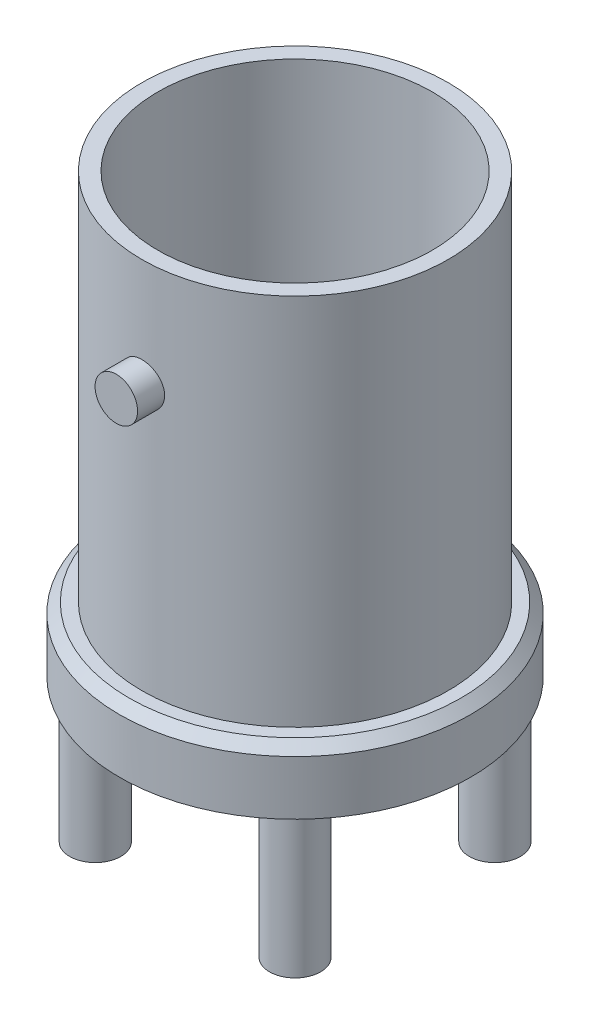
SolidWorks part; units mm, degrees
note: The reader was unsure of these and kept them because the rebuilt part matched: shared geometry of "Sketch5<3>".
ref_plane "Front Plane" through (0, 0, 0) normal (0, 0, 1) x (1, 0, 0)
ref_plane "Top Plane" through (0, 0, 0) normal (0, 1, 0) x (1, 0, 0)
ref_plane "Right Plane" through (0, 0, 0) normal (1, 0, 0) x (0, 0, -1)
sketch "Sketch1" plane through (0, 0, 0) normal (1, 0, 0) x (0, 0, -1)
  line L0 (0, 0) -> (0, 2)
  line L1 (4.3, 13.7) -> (4.8, 13.7)
  line L2 (4.8, 13.7) -> (4.8, 2)
  line L3 (4.8, 2) -> (5.5, 2)
  line L5 (5.5, 2) -> (5.5, 0)
  line L6 (5.5, 0) -> (0, 0)
  line L7 (4.3, 13.7) -> (4.3, 2)
  line L8 (4.3, 2) -> (1.7239, 2)
  line L9 (1.7239, 2) -> (1.7239, 9.3845)
  line L10 (1.7239, 9.3845) -> (0.2863, 9.3845)
  line L11 (0.2863, 9.3845) -> (0.2863, 2)
  line L14 (0.2863, 2) -> (0, 2)
  dimension "D1" = 5.5
  dimension "D2" = 4.8
  dimension "D3" = 2
  dimension "D4" = 13.7
  dimension "D5" = 0.5
revolve "Revolve1" add sketch "Sketch1" angle 360 about L0
ref_plane "Plane1" through (0, 0, 4.8) normal (0, 0, 1) x (1, 0, 0)
sketch "Sketch4" plane through (0, 0, 4.8) normal (0, 0, 1) x (1, 0, 0)
  line L0 (0, 2) -> (0, 10.3204) construction
  line L1 (5.5, 2) -> (-5.5, 2) construction
  circle A0 centre (0, 10.3204) radius 0.6662
extrude "Boss-Extrude1" add sketch "Sketch4" along normal blind 0.8 and the other way up to surface
ref_plane "Plane2" through (0, 0, -4.8) normal (0, 0, -1) x (-1, 0, 0)
ref_plane "Plane3" through (0, 0, 0) normal (0, 0, -1) x (-1, 0, 0)
mirror "Mirror1" about plane through (0, 0, 0) normal (0, 0, -1) of "Boss-Extrude1"
chamfer "Chamfer1" distance 0.3 angle 45 1 edges at (0, 2, -5.5)
fillet "Fillet1" radius 0.2 1 edges at (0, 9.3845, -0.2863)
chamfer "Chamfer2" distance 0.4 angle 45 1 edges at (0, 9.3845, -1.7239)
sketch "Sketch5" plane through (0, 0, 0) normal (0, -1, 0) x (1, 0, 0)
  circle A0 centre (0, 0) radius 0.55
  circle A1 centre (-3.13, 3.13) radius 0.8
  circle A2 centre (3.13, 3.13) radius 0.8
  circle A3 centre (3.13, -3.13) radius 0.8
  circle A4 centre (-3.13, -3.13) radius 0.8
  point P14 (0, 0)
  dimension "D2" = 1.6
  dimension "D3" = 1.1
  dimension "D1" = 3.13
  dimension "D5" = 3.13
  dimension "D4" = 4
extrude "Boss-Extrude2" add sketch "Sketch5" along normal blind 4.9 contours A0
extrude "Boss-Extrude3" add sketch "Sketch5<3>" along normal blind 4.5 contours A1 | A2 | A4 | A3
sketch "Sketch5<3>" plane through (0, 0, 0) normal (0, -1, 0) x (1, 0, 0) same geometry as "Sketch5"
